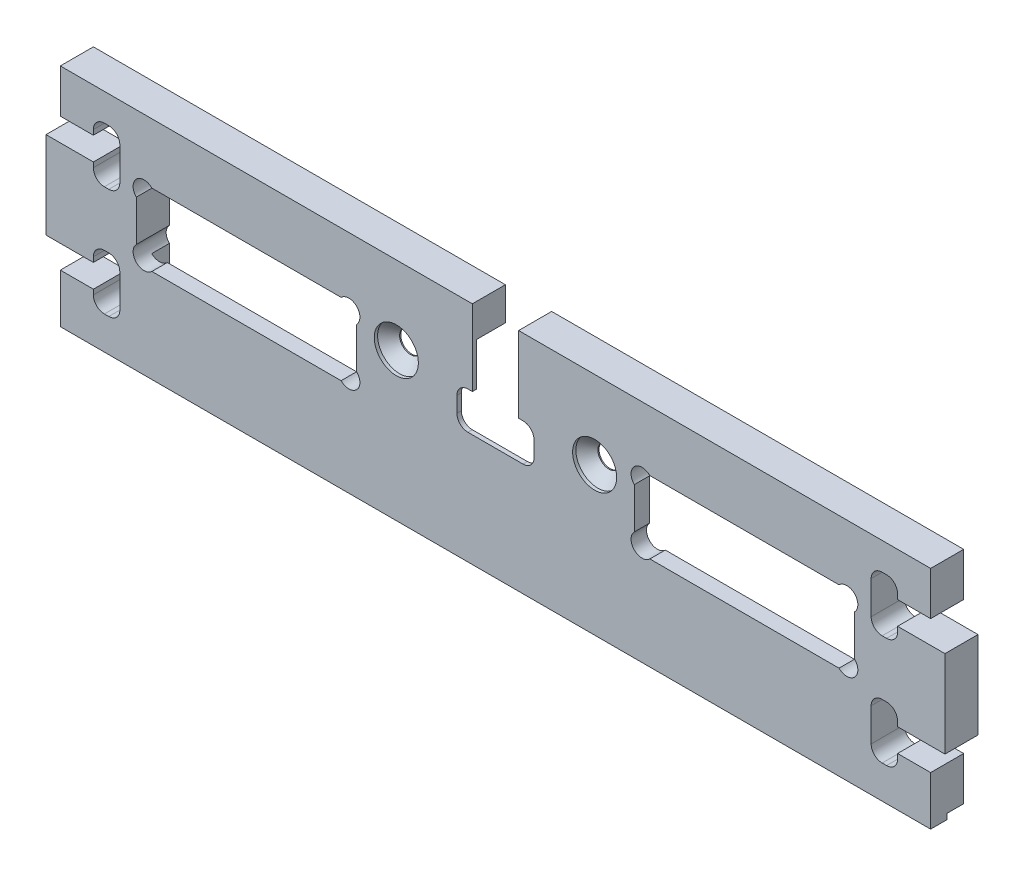
SolidWorks part; units mm, degrees
ref_plane "Front Plane" through (0, 0, 0) normal (0, 0, 1) x (1, 0, 0)
ref_plane "Top Plane" through (0, 0, 0) normal (0, 1, 0) x (1, 0, 0)
ref_plane "Right Plane" through (0, 0, 0) normal (1, 0, 0) x (0, 0, -1)
sketch "Sketch1" plane through (0, 0, 0) normal (0, 0, 1) x (1, 0, 0)
  line L0 (-39.5, 0) -> (39.5, 0) construction
  line L1 (-39.5, 10) -> (39.5, 10)
  line L2 (-39.5, 10) -> (-39.5, -10)
  line L3 (-39.5, -10) -> (39.5, -10)
  line L4 (39.5, 10) -> (39.5, -10)
  line L5 (-39.5, 10) -> (39.5, -10) construction
  line L6 (-39.5, -10) -> (39.5, 10) construction
  line L7 (0, 10) -> (0, -10) construction
  line L9 (-40.8, -3.95) -> (-39.5, -3.95)
  line L10 (-40.8, -3.95) -> (-40.8, 3.95)
  line L11 (-40.8, 3.95) -> (-39.5, 3.95)
  line L12 (-39.5, -3.95) -> (-39.5, 3.95)
  line L13 (-40.8, -3.95) -> (-39.5, 3.95) construction
  line L14 (-40.8, 3.95) -> (-39.5, -3.95) construction
  line L16 (40.8, 3.95) -> (39.5, 3.95)
  line L17 (40.8, -3.95) -> (40.8, 3.95)
  line L18 (40.8, -3.95) -> (39.5, -3.95)
  line L19 (-39.5, 5) -> (39.5, 5) construction
  line L20 (-35.3, 7.5) -> (-35.3, 2.5) construction
  line L21 (-36.5, 3.95) -> (-39.5, 3.95)
  line L22 (-36.5, 3.95) -> (-36.5, 6.05)
  line L23 (-36.5, 6.05) -> (-39.5, 6.05)
  line L24 (-39.5, 3.95) -> (-39.5, 6.05)
  line L25 (-36.5, 3.95) -> (-39.5, 6.05) construction
  line L26 (-36.5, 6.05) -> (-39.5, 3.95) construction
  line L27 (-34.1, 7.5) -> (-36.5, 7.5)
  line L28 (-34.1, 7.5) -> (-34.1, 2.5)
  line L29 (-34.1, 2.5) -> (-36.5, 2.5)
  line L30 (-36.5, 7.5) -> (-36.5, 2.5)
  line L31 (-34.1, 7.5) -> (-36.5, 2.5) construction
  line L32 (-34.1, 2.5) -> (-36.5, 7.5) construction
  line L33 (-34.1, -7.5) -> (-36.5, -7.5)
  line L34 (-34.1, -7.5) -> (-34.1, -2.5)
  line L35 (-34.1, -2.5) -> (-36.5, -2.5)
  line L36 (-36.5, -7.5) -> (-36.5, -2.5)
  line L37 (-36.5, -3.95) -> (-39.5, -3.95)
  line L38 (-36.5, -6.05) -> (-39.5, -6.05)
  line L39 (36.5, 3.95) -> (39.5, 3.95)
  line L40 (36.5, 6.05) -> (39.5, 6.05)
  line L41 (36.5, 7.5) -> (36.5, 2.5)
  line L42 (34.1, 7.5) -> (36.5, 7.5)
  line L43 (34.1, 7.5) -> (34.1, 2.5)
  line L44 (34.1, 2.5) -> (36.5, 2.5)
  line L45 (34.1, -2.5) -> (36.5, -2.5)
  line L46 (34.1, -7.5) -> (34.1, -2.5)
  line L47 (34.1, -7.5) -> (36.5, -7.5)
  line L48 (36.5, -7.5) -> (36.5, -2.5)
  line L49 (36.5, -6.05) -> (39.5, -6.05)
  line L50 (36.5, -3.95) -> (39.5, -3.95)
  point P0 (0, 0)
  point P10 (-40.15, 0)
  point P15 (-38, 5)
  point P35 (-35.3, 5)
  dimension "D1" = 79
  dimension "D2" = 20
  dimension "D4" = 1.3
  dimension "D7" = 5
  dimension "D8" = 2.1
  dimension "D9" = 3
  dimension "D10" = 2.4
  dimension "D11" = 5
extrude "Base shape" add sketch "Sketch1" along normal blind 3 contours L4 L1 L2 L3 | L9 L2 L11 L10 | L16 L4 L18 L17 region at (0, 0, 0) region at (-40.15, 0, 0) region at (40.15, 0, 0)
sketch "Sketch4" plane through (0, -10, 0) normal (0, -1, 0) x (1, 0, 0)
  line L0 (39.5, 3) -> (39.5, 0) construction
  line L1 (-39.5, 3) -> (39.5, 3)
  line L2 (-39.5, 3) -> (-39.5, 1.5)
  line L3 (-39.5, 1.5) -> (39.5, 1.5)
  line L4 (39.5, 3) -> (39.5, 1.5)
extrude "Floor lip" add sketch "Sketch4" along normal blind 0.5
sketch "Sketch6" plane through (0, 0, 0) normal (0, 0, -1) x (-1, 0, 0)
  line L0 (0, 0) -> (0, -10) construction
  line L1 (39.5, -10) -> (-39.5, -10) construction
  line L2 (-4, -10) -> (4, -10) construction
  line L3 (39.5, -10) -> (-39.5, -10) construction
  line L4 (-4, -9) -> (4, -9)
  line L5 (-4, -11) -> (4, -11)
  arc A0 (-4, -9) -> (-4, -11) centre (-4, -10) ccw
  arc A1 (4, -11) -> (4, -9) centre (4, -10) ccw
  point P9 (0, -10)
  dimension "D1" = 2
  dimension "D2" = 8
extrude "Nail cutout" cut sketch "Sketch6" against normal up to surface (1.5 mm away) up to face at (0, -10.25, 1.5)
sketch "Sketch3" plane through (-40.8, 0, 0) normal (-1, 0, 0) x (0, 0, 1)
  line L0 (0, 6.05) -> (3, 3.95) construction
  line L1 (0, 6.05) -> (3, 6.05)
  line L2 (0, 6.05) -> (0, 3.95)
  line L3 (0, 3.95) -> (3, 3.95)
  line L4 (3, 6.05) -> (3, 3.95)
  line L5 (0, -3.95) -> (3, -6.05) construction
  line L6 (0, -3.95) -> (3, -3.95)
  line L7 (0, -3.95) -> (0, -6.05)
  line L8 (0, -6.05) -> (3, -6.05)
  line L9 (3, -3.95) -> (3, -6.05)
  point P6 (1.5, 5)
  point P13 (1.5, -5)
ref_axis "Tap axis top" through (-53.7846, 5, 1.5) along (1, 0, 0)
ref_axis "Tap axis bottom" through (-54.2844, -5, 1.5) along (1, 0, 0)
fillet "Mill fillets" radius 1 16 edges at (36.5, -7.5, 1.5) (36.5, 2.5, 1.5) (34.1, 2.5, 1.5) (34.1, -7.5, 1.5) (36.5, -2.5, 1.5) (36.5, 7.5, 1.5) (34.1, -2.5, 1.5) (34.1, 7.5, 1.5) (-36.5, -2.5, 1.5) (-34.1, -2.5, 1.5) (-34.1, -7.5, 1.5) (-36.5, -7.5, 1.5) (-36.5, 2.5, 1.5) (-34.1, 2.5, 1.5) (-34.1, 7.5, 1.5) (-36.5, 7.5, 1.5)
sketch "Sketch8" [suppressed] plane through (0, 0, 3) normal (0, 0, 1) x (1, 0, 0)
  line L0 (-40.8, 0) -> (40.8, 0) construction
  line L1 (-40.8, -3.95) -> (-40.8, 3.95) construction
  line L2 (40.8, -3.95) -> (40.8, 3.95) construction
  line L4 (-24.5, 5.15) -> (24.5, 5.15)
  line L5 (-25.5, 4.15) -> (-25.5, -4.15)
  line L6 (-24.5, -5.15) -> (24.5, -5.15)
  line L7 (25.5, 4.15) -> (25.5, -4.15)
  line L8 (-25.5, 5.15) -> (25.5, -5.15) construction
  line L9 (-25.5, -5.15) -> (25.5, 5.15) construction
  arc A0 (24.5, -5.15) -> (25.5, -4.15) centre (24.5, -4.15) ccw
  arc A1 (24.5, 5.15) -> (25.5, 4.15) centre (24.5, 4.15) cw
  arc A2 (-25.5, -4.15) -> (-24.5, -5.15) centre (-24.5, -4.15) ccw
  arc A3 (-24.5, 5.15) -> (-25.5, 4.15) centre (-24.5, 4.15) ccw
  point P6 (0, 0)
  dimension "D3" = 1
  dimension "D1" = 51
  dimension "D2" = 10.3
extrude "Led strip pocket" [suppressed] cut sketch "Sketch8" against normal offset from surface (2.5 mm away) 0.5 up to face at (0, -0.6712, 0)
sketch "Sketch9" [suppressed] plane through (0, 0, 0.5) normal (0, 0, 1) x (1, 0, 0)
  line L0 (-19.5, 5.15) -> (-19.5, -5.15)
  line L1 (0, 5.15) -> (0, -5.15) construction
  line L2 (19.5, 5.15) -> (19.5, -5.15)
  line L3 (-25.5, -2.978) -> (25.5, -2.978) construction
  line L4 (25.5, -4.15) -> (25.5, 4.15)
  line L5 (24.5, 5.15) -> (-24.5, 5.15)
  line L6 (-25.5, 4.15) -> (-25.5, -4.15)
  line L7 (-24.5, -5.15) -> (24.5, -5.15)
  line L8 (25.5, -4.15) -> (25.5, 4.15)
  line L9 (24.5, 5.15) -> (-24.5, 5.15)
  line L10 (-25.5, 4.15) -> (-25.5, -4.15)
  line L11 (-24.5, -5.15) -> (24.5, -5.15)
  circle A0 centre (-12.7, -2.978) radius 1
  circle A1 centre (12.7, -2.978) radius 1
  arc A4 (24.5, -5.15) -> (25.5, -4.15) centre (24.5, -4.15) ccw
  arc A5 (25.5, 4.15) -> (24.5, 5.15) centre (24.5, 4.15) ccw
  arc A6 (-24.5, 5.15) -> (-25.5, 4.15) centre (-24.5, 4.15) ccw
  arc A7 (-25.5, -4.15) -> (-24.5, -5.15) centre (-24.5, -4.15) ccw
  arc A8 (24.5, -5.15) -> (25.5, -4.15) centre (24.5, -4.15) ccw
  arc A9 (25.5, 4.15) -> (24.5, 5.15) centre (24.5, 4.15) ccw
  arc A10 (-24.5, 5.15) -> (-25.5, 4.15) centre (-24.5, 4.15) ccw
  arc A11 (-25.5, -4.15) -> (-24.5, -5.15) centre (-24.5, -4.15) ccw
  arc M13 (24.5, -5.15) -> (25.5, -4.15) centre (24.5, -4.15) ccw
  line M14 (25.5, -4.15) -> (25.5, 4.15)
  arc M15 (25.5, 4.15) -> (24.5, 5.15) centre (24.5, 4.15) ccw
  line M16 (24.5, 5.15) -> (-24.5, 5.15)
  arc M17 (-24.5, 5.15) -> (-25.5, 4.15) centre (-24.5, 4.15) ccw
  line M18 (-25.5, 4.15) -> (-25.5, -4.15)
  arc M19 (-25.5, -4.15) -> (-24.5, -5.15) centre (-24.5, -4.15) ccw
  line M20 (-24.5, -5.15) -> (24.5, -5.15)
  dimension "D4" = 2
  dimension "D2" = 6
  dimension "D3" = 8.128
  dimension "D5" = 25.4
  dimension "D1" = 0
extrude "Led strip cuts" [suppressed] cut sketch "Sketch9" against normal up to next contours L0 M16 M17 M18 M19 M20 | L2 M16 M20 M13 M14 M15 | A0 | A1
fillet "Led strip cut fillets" [suppressed] radius 1
sketch "Sketch13" plane through (0, 0, 0) normal (0, 0, -1) x (-1, 0, 0)
  line L0 (0, 15.8648) -> (0, -21.9195) construction
  line L2 (-4.1, -5.7) -> (4.1, -5.7)
  line L3 (-5.1, -4.7) -> (-5.1, 6)
  line L4 (-4.1, 7) -> (4.1, 7)
  line L5 (5.1, -4.7) -> (5.1, 6)
  line L6 (-5.1, -5.7) -> (5.1, 7) construction
  line L7 (-5.1, 7) -> (5.1, -5.7) construction
  line L10 (39.5, 10) -> (-39.5, 10) construction
  arc A0 (-4.1, -5.7) -> (-5.1, -4.7) centre (-4.1, -4.7) cw
  arc A1 (4.1, -5.7) -> (5.1, -4.7) centre (4.1, -4.7) ccw
  arc A4 (5.1, 6) -> (4.1, 7) centre (4.1, 6) ccw
  arc A5 (-5.1, 6) -> (-4.1, 7) centre (-4.1, 6) cw
  point P1 (0, 0.65)
  dimension "D4" = 1
  dimension "D5" = 1
  dimension "D1" = 10.2
  dimension "D2" = 12.7
  dimension "D3" = 3
extrude "Bumper mount inner cut" cut sketch "Sketch13" against normal offset from surface (2.6 mm away) 0.4 up to face at (0, -0.0192, 3)
sketch "Sketch14" plane through (0, 0, 0) normal (0, 0, -1) x (-1, 0, 0)
  line L1 (0, 12.9528) -> (0, -14.0841) construction
  line L2 (4.1, 7) -> (-4.1, 7) construction
  line L3 (-4.1, -5.7) -> (4.1, -5.7) construction
  line L4 (-11.6, 7) -> (11.6, 7)
  line L5 (-12.6, 6) -> (-12.6, -4.7)
  line L6 (-11.6, -5.7) -> (11.6, -5.7)
  line L7 (12.6, 6) -> (12.6, -4.7)
  line L8 (-12.6, 7) -> (12.6, -5.7) construction
  line L9 (-12.6, -5.7) -> (12.6, 7) construction
  arc A1 (11.6, -5.7) -> (12.6, -4.7) centre (11.6, -4.7) ccw
  arc A2 (-12.6, -4.7) -> (-11.6, -5.7) centre (-11.6, -4.7) ccw
  arc A3 (11.6, 7) -> (12.6, 6) centre (11.6, 6) cw
  arc A4 (-12.6, 6) -> (-11.6, 7) centre (-11.6, 6) cw
  point P6 (0, 0.65)
  dimension "D2" = 1
  dimension "D3" = 1
  dimension "D1" = 25.2
extrude "Bumper mount outer cut" cut sketch "Sketch14" against normal blind 1.6
sketch "Sketch15" plane through (0, 0, 1.6) normal (0, 0, -1) x (-1, 0, 0)
  line L0 (-12.6, 2.9) -> (12.6, 2.9) construction
  line L3 (0, 16.4744) -> (0, -20.0474) construction
  line L7 (-12.6, 6) -> (-12.6, -4.7) construction
  line L8 (12.6, -4.7) -> (12.6, 6) construction
  line L11 (-4.1, 7) -> (-11.6, 7) construction
  circle A0 centre (-9, 2.9) radius 1
  circle A1 centre (9, 2.9) radius 1
  dimension "D1" = 18
  dimension "D2" = 2
  dimension "D3" = 4.1
extrude "Bumper mount screw holes" cut sketch "Sketch15" against normal up to next
sketch "Sketch16" plane through (0, 0, 2.6) normal (0, 0, -1) x (-1, 0, 0)
  line L0 (-5.1, 1.4) -> (5.1, 1.4) construction
  line L3 (0, 7) -> (0, -4.2) construction
  line L4 (-2.5, 3.1) -> (2.5, 3.1)
  line L5 (-3.5, 2.1) -> (-3.5, 0.7)
  line L6 (-2.5, -0.3) -> (2.5, -0.3)
  line L7 (3.5, 2.1) -> (3.5, 0.7)
  line L8 (-3.5, 3.1) -> (3.5, -0.3) construction
  line L9 (-3.5, -0.3) -> (3.5, 3.1) construction
  line L11 (-5.1, 6) -> (-5.1, -4.7) construction
  line L13 (4.1, 7) -> (-4.1, 7) construction
  arc A0 (2.5, -0.3) -> (3.5, 0.7) centre (2.5, 0.7) ccw
  arc A1 (-3.5, 0.7) -> (-2.5, -0.3) centre (-2.5, 0.7) ccw
  arc A2 (-2.5, 3.1) -> (-3.5, 2.1) centre (-2.5, 2.1) ccw
  arc A3 (2.5, 3.1) -> (3.5, 2.1) centre (2.5, 2.1) cw
  point P6 (0, 1.4)
  dimension "D3" = 1
  dimension "D1" = 7
  dimension "D2" = 3.4
  dimension "D4" = 11.2
extrude "Bumper body cut" cut sketch "Sketch16" against normal up to next
hole_wizard "Bumper screw countersunks" positions "Sketch17" profile "Sketch18" countersink size "M2" standard "ANSI Metric" end condition through all
sketch "Sketch17" plane through (0, 0, 3) normal (0, 0, 1) x (1, 0, 0)
  point P0 (9, 2.9)
  point P3 (-9, 2.9)
sketch "Sketch18" plane through (9, 2.9, 3) normal (1, 0, 0) x (0, -1, 0)
  line L0 (0, 0) -> (0, 3)
  line L1 (0, 3) -> (1, 3)
  line L2 (1, 3) -> (1, 1.3)
  line L3 (1, 1.3) -> (2, 0.3)
  line L4 (2, 0.3) -> (2, 0)
  line L6 (2, 0) -> (0, 0)
  line L7 (-1, 1.3) -> (-2, 0.3) construction
  line L11 (0, -6.35) -> (0, 107.95) construction
  dimension "Thru Hole Dia." = 2
  dimension "Thru Hole Depth" = 3
  dimension "C'Sink Dia." = 4
  dimension "C'Sink Angle" = 90
  dimension "Head Clearance" = 0.3
sketch "Sketch19" plane through (0, 0, 0) normal (0, 0, -1) x (-1, 0, 0)
  line L0 (0, 15.6498) -> (0, -12.9575) construction
  line L1 (39.5, 10) -> (-39.5, 10) construction
  line L2 (-2.1, 3.1) -> (2.1, 3.1)
  line L3 (-2.1, 3.1) -> (-2.1, 10)
  line L4 (-2.1, 10) -> (2.1, 10)
  line L5 (2.1, 3.1) -> (2.1, 10)
  line L6 (-2.1, 3.1) -> (2.1, 10) construction
  line L7 (-2.1, 10) -> (2.1, 3.1) construction
  line L8 (2.5, 3.1) -> (-2.5, 3.1) construction
  point P1 (0, 6.55)
  dimension "D1" = 4.2
extrude "Bumper insertion cut" cut sketch "Sketch19" against normal up to next
sketch "Sketch20" plane through (0, 0, 0) normal (0, 0, -1) x (-1, 0, 0)
  line L0 (-12.6, 6) -> (-12.6, -4.7) construction
  line L1 (-12.6, 4.55) -> (-32.6, 4.55)
  line L2 (-12.6, 4.55) -> (-12.6, -2)
  line L3 (-12.6, -2) -> (-32.6, -2)
  line L4 (-32.6, 4.55) -> (-32.6, -2)
  line L5 (-2.1, 10) -> (-39.5, 10) construction
  line L6 (-12.6, 4.55) -> (-19.15, -2) construction
  line L7 (-22.6, 4.55) -> (-22.6, -2) construction
  line L8 (-32.6, 1.275) -> (-12.6, 1.275) construction
  line L9 (0, 16.176) -> (0, -15.99) construction
  line L10 (12.6, 4.55) -> (12.6, -2)
  line L11 (12.6, -2) -> (32.6, -2)
  line L12 (32.6, 4.55) -> (32.6, -2)
  line L13 (12.6, 4.55) -> (32.6, 4.55)
  circle A0 centre (-13.3071, 3.8429) radius 1
  circle A1 centre (-31.8929, 3.8429) radius 1
  circle A2 centre (-13.3071, -1.2929) radius 1
  circle A3 centre (-31.8929, -1.2929) radius 1
  circle A4 centre (13.3071, 3.8429) radius 1
  circle A5 centre (13.3071, -1.2929) radius 1
  circle A6 centre (31.8929, -1.2929) radius 1
  circle A7 centre (31.8929, 3.8429) radius 1
  dimension "D5" = 2
  dimension "D1" = 20
  dimension "D2" = 5.45
  dimension "D3" = 6.55
  dimension "D4" = 45
extrude "Bumper switches cut" cut sketch "Sketch20" against normal up to next contours L1 L4 L3 L2 | A1 | A3 | A0 | A2 | L13 L12 L11 L10 | A4 | A5 | A6 | A7
sketch "Sketch21" plane through (0, 0, 0) normal (0, 0, -1) x (-1, 0, 0)
  line L0 (-14.0142, -2) -> (-31.1858, -2) construction
  line L1 (-32.6, -2) -> (-12.6, -2)
  line L2 (-32.6, -2) -> (-32.6, -5.7)
  line L3 (-32.6, -5.7) -> (-12.6, -5.7)
  line L4 (-12.6, -2) -> (-12.6, -5.7)
  line L5 (-12.6, -2) -> (-12.6, -4.7) construction
  line L6 (-11.6, -5.7) -> (-4.1, -5.7) construction
  line L7 (-32.6, 3.1358) -> (-32.6, -0.5858) construction
  line L8 (-12.6, -5.7) -> (-11.6, -5.7)
  line L9 (-32.6, -5.7) -> (-28.9, -2) construction
  line L10 (0, 14.2019) -> (0, -15.3745) construction
  line L11 (12.6, -5.7) -> (11.6, -5.7)
  line L12 (12.6, -2) -> (12.6, -5.7)
  line L13 (32.6, -2) -> (12.6, -2)
  line L14 (32.6, -2) -> (32.6, -5.7)
  line L15 (32.6, -5.7) -> (12.6, -5.7)
  arc A0 (-12.6, -4.7) -> (-11.6, -5.7) centre (-11.6, -4.7) ccw construction
  arc A1 (-12.6, -4.7) -> (-11.6, -5.7) centre (-11.6, -4.7) ccw
  circle A2 centre (-31.8929, -4.9929) radius 1
  arc A3 (-32.6, -0.5858) -> (-31.1858, -2) centre (-31.8929, -1.2929) ccw construction
  circle A4 centre (31.8929, -4.9929) radius 1
  arc A5 (12.6, -4.7) -> (11.6, -5.7) centre (11.6, -4.7) cw
  dimension "D1" = 45
extrude "Bumper switch mounts cut" cut sketch "Sketch21" against normal up to surface (1.6 mm away) contours A1 L4 L8 | L12 A5 L11 | L4 L1 L2 L3 | A2 | L12 L13 L14 L15 | A4 region at (12.3766, -5.4766, 0) region at (-12.3766, -5.4766, 0) up to face at (-8, 2.9, 1.6)
sketch "Outer coordinate system sketch" plane through (0, 0, 3) normal (0, 0, 1) x (1, 0, 0)
  line L0 (-35.3, 7.5) -> (-35.3, 2.5) construction
  line L1 (-35.1, 7.5) -> (-35.5, 7.5) construction
  line L2 (-40.8, 3.95) -> (-40.8, 10) construction
  line L3 (-40.8, 10) -> (-39.5, 10) construction
  line L4 (-35.1, 2.5) -> (-35.5, 2.5) construction
  line L5 (0, 15.526) -> (0, -17.3739) construction
  line L6 (-51.2617, 0) -> (56.0692, 0) construction
  circle A0 centre (-35.3, 6.5) radius 1
  point P16 (-35.3, 6.5)
  point P20 (0, 0)
  point P22 (35.3, 6.5)
  point P23 (0, 0)
  point P24 (-35.3, -6.5)
  point P25 (35.3, -6.5)
  dimension "D1" = 2
sketch "Inner coordinate system sketch" plane through (0, 0, 0) normal (0, 0, 1) x (1, 0, 0)
  line L0 (-40.8, -3.95) -> (-40.8, -10) construction
  line L1 (-40.8, -10) -> (-39.5, -10) construction
  line L3 (0, 19.9465) -> (0, -19.5427) construction
  line L4 (53.9633, 0) -> (-51.6097, 0) construction
  point P1 (0, 0)
  point P4 (0, 0)
  point P5 (0, 0)
  point P6 (0, 0)
  point P9 (0, 0)
  point P11 (0, 0)
  point P15 (-39.5, -10)
sketch "Deep inner pocket mill sketch" plane through (0, 0, 2.6) normal (0, 0, -1) x (-1, 0, 0)
  line L0 (-4.1, 7) -> (4.1, 7)
  line L12 (4.1, 7) -> (2.1, 7)
  line L13 (2.1, 7) -> (2.1, 3.1)
  line L14 (2.1, 3.1) -> (2.5, 3.1)
  line L15 (3.5, 2.1) -> (3.5, 0.7)
  line L16 (2.5, -0.3) -> (-2.5, -0.3)
  line L17 (-3.5, 0.7) -> (-3.5, 2.1)
  line L18 (-2.5, 3.1) -> (-2.1, 3.1)
  line L19 (-2.1, 3.1) -> (-2.1, 7)
  line L20 (-2.1, 7) -> (-4.1, 7)
  line L21 (-5.1, 6) -> (-5.1, -4.7)
  line L22 (-4.1, -5.7) -> (4.1, -5.7)
  line L23 (5.1, -4.7) -> (5.1, 6)
  line L33 (-5.1, 6) -> (-5.1, -4.7)
  line L34 (-4.1, -5.7) -> (4.1, -5.7)
  line L35 (5.1, -4.7) -> (5.1, 6)
  arc A8 (3.5, 2.1) -> (2.5, 3.1) centre (2.5, 2.1) ccw
  arc A9 (2.5, -0.3) -> (3.5, 0.7) centre (2.5, 0.7) ccw
  arc A10 (-3.5, 0.7) -> (-2.5, -0.3) centre (-2.5, 0.7) ccw
  arc A11 (-2.5, 3.1) -> (-3.5, 2.1) centre (-2.5, 2.1) ccw
  arc A12 (-4.1, 7) -> (-5.1, 6) centre (-4.1, 6) ccw
  arc A13 (-5.1, -4.7) -> (-4.1, -5.7) centre (-4.1, -4.7) ccw
  arc A14 (4.1, -5.7) -> (5.1, -4.7) centre (4.1, -4.7) ccw
  arc A15 (5.1, 6) -> (4.1, 7) centre (4.1, 6) ccw
  arc A20 (-4.1, 7) -> (-5.1, 6) centre (-4.1, 6) ccw
  arc A21 (-5.1, -4.7) -> (-4.1, -5.7) centre (-4.1, -4.7) ccw
  arc A22 (4.1, -5.7) -> (5.1, -4.7) centre (4.1, -4.7) ccw
  arc A23 (5.1, 6) -> (4.1, 7) centre (4.1, 6) ccw
  dimension "D1" = 0
sketch "Shallow inner pocket mill sketch" plane through (0, 0, 1.6) normal (0, 0, -1) x (-1, 0, 0)
  line L2 (12.6, 4.55) -> (12.6, 6) construction
  line L7 (-12.6, 6) -> (-12.6, 4.55) construction
  line L16 (12.6, 4.55) -> (12.6, 6)
  line L21 (-12.6, 6) -> (-12.6, 4.55)
  line L42 (-32.6, -1) -> (-13.6, -1)
  line L43 (-12.6, 3.1358) -> (-12.6, -0.5858) construction
  line L47 (0, 16.1275) -> (0, -14.7685) construction
  line L53 (-31.1858, -5.7) -> (31.1858, -5.7)
  line L54 (-11.6, 7) -> (11.6, 7)
  line L55 (-12.6, 4.55) -> (-13.6, 4.55)
  line L56 (-13.6, 4.55) -> (-13.6, -1)
  line L58 (-22.6, -2) -> (-22.6, -1) construction
  line L59 (-31.1858, -2) -> (-14.0142, -2) construction
  line L60 (-12.6, 1.275) -> (-13.6, 1.275) construction
  line L61 (-32.6, -1) -> (-32.6, -4.2858)
  line L62 (12.6, 4.55) -> (13.6, 4.55)
  line L63 (13.6, 4.55) -> (13.6, -1)
  line L64 (32.6, -1) -> (13.6, -1)
  line L65 (32.6, -1) -> (32.6, -4.2858)
  arc A2 (12.6, 6) -> (11.6, 7) centre (11.6, 6) ccw construction
  arc A5 (31.1858, -5.7) -> (32.6, -4.2858) centre (31.8929, -4.9929) ccw construction
  arc A10 (-32.6, -4.2858) -> (-31.1858, -5.7) centre (-31.8929, -4.9929) ccw construction
  arc A13 (-11.6, 7) -> (-12.6, 6) centre (-11.6, 6) ccw construction
  arc A16 (12.6, 6) -> (11.6, 7) centre (11.6, 6) ccw
  arc A19 (31.1858, -5.7) -> (32.6, -4.2858) centre (31.8929, -4.9929) ccw
  arc A24 (-32.6, -4.2858) -> (-31.1858, -5.7) centre (-31.8929, -4.9929) ccw
  arc A27 (-11.6, 7) -> (-12.6, 6) centre (-11.6, 6) ccw
  dimension "D1" = 1
